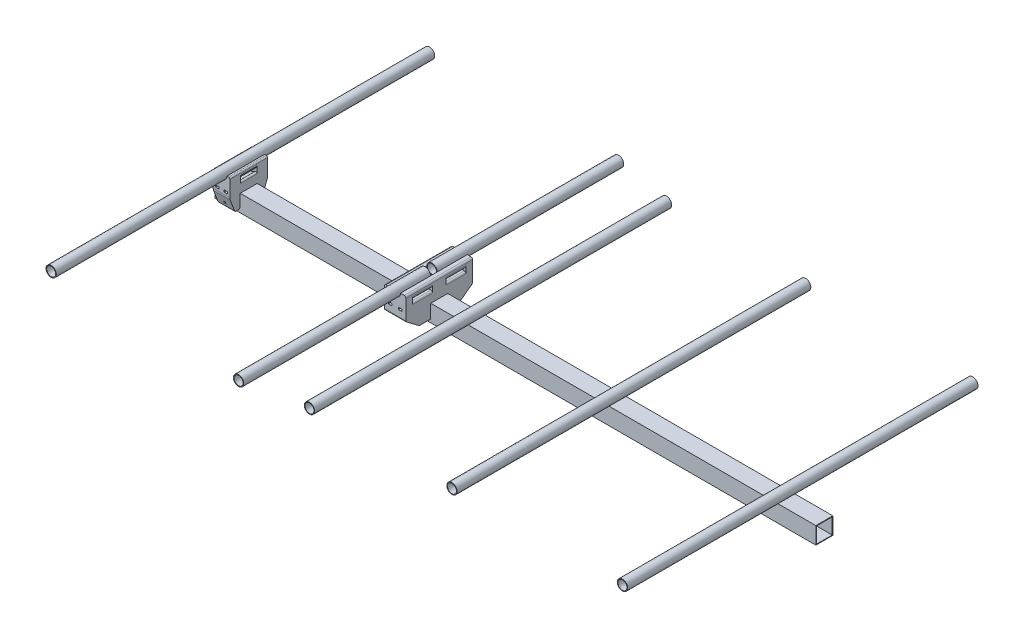
SolidWorks part; units mm, degrees
note: The reader was unsure of these and kept them because the rebuilt part matched: shared geometry of "Element Geometry<4>", "Element Geometry<5>", "Element Geometry<6>", "Element Geometry<7>".
other "Antenna Beam" parameters "D6"=81.8924, "D1"=79.9358, "D2"=111.825, "D3"=337.3911, "D4"=313.7423, "D5"=328.3888, "D7"=835, "D8"=23.25
ref_plane "Front Plane" through (0, 0, 0) normal (0, 0, 1) x (1, 0, 0)
ref_plane "Top Plane" through (0, 0, 0) normal (0, 1, 0) x (1, 0, 0)
ref_plane "Right Plane" through (0, 0, 0) normal (1, 0, 0) x (0, 0, -1)
sketch3d "3DSketch1"
  line L0 (-450, 0, 0) -> (450, 0, 0)
  point P4 (0, 0, 0)
  dimension "D1" = 900
other "Al tube square AL TUBE 1 SQR X 0.035 WALL(2)"
ref_plane "Plane2" through (-450, 0, 0) normal (1, 0, 0) x (0, 0, -1)
sketch "Sketch1" plane through (-450, 0, 0) normal (1, 0, 0) x (0, 0, -1)
  line L0 (-11.811, -11.811) -> (-11.811, 11.811)
  line L1 (11.811, 11.811) -> (-11.811, 11.811)
  line L2 (11.811, 11.811) -> (11.811, -11.811)
  line L3 (-11.811, -11.811) -> (11.811, -11.811)
  line L4 (-12.7, -12.7) -> (12.7, -12.7)
  line L5 (-12.7, -12.7) -> (-12.7, 12.7)
  line L6 (12.7, 12.7) -> (-12.7, 12.7)
  line L7 (12.7, 12.7) -> (12.7, -12.7)
  line L8 (0, -11.811) -> (0, -12.7) construction
  line L9 (0, -11.811) -> (0, 11.811) construction
  line L10 (0, 11.811) -> (0, 12.7) construction
  line L11 (12.7, 0) -> (11.811, 0) construction
  line L12 (11.811, 0) -> (-11.811, 0) construction
  line L13 (-11.811, 0) -> (-12.7, 0) construction
  point P14 (0, 0)
  point P17 (0, 0)
  dimension "Thickness" = 0.889
  dimension "V_leg" = 25.4
  dimension "H_leg" = 25.4
sketch "Element Geometry" plane through (0, 0, 0) normal (0, 0, 1) x (1, 0, 0)
  line L0 (-425, 113.5751) -> (-425, -79.8489) construction
  line L2 (-143, 160.4967) -> (-143, -91.5114) construction
  line L3 (-54, 179.3838) -> (-54, -96.4018) construction
  line L4 (157, 132.9645) -> (157, -180.7778) construction
  line L5 (-450, 12.7) -> (-450, -12.7) construction
  line L6 (410, 132.9645) -> (410, -195.4242) construction
  line L7 (-425, 40.45) -> (410, 40.45) construction
  line L11 (424.2916, 32.7) -> (387.9179, 32.7) construction
  line L12 (450, 12.7) -> (-450, 12.7) construction
  circle A0 centre (410, 40.45) radius 7.75
  circle A1 centre (157, 40.45) radius 7.75
  circle A2 centre (-425, 40.45) radius 7.75
  circle A3 centre (-143, 40.45) radius 7.75
  circle A4 centre (-54, 40.45) radius 7.75
  point P13 (157, 40.45)
  point P14 (-143, 40.45)
  point P18 (-54, 40.45)
  dimension "D2" = 282
  dimension "D3" = 371
  dimension "D4" = 582
extrude "Reflector Geometry" add sketch "Element Geometry" along normal mid plane 567 separate body contours A2
extrude "Director Geometry #1" add sketch "Element Geometry<4>" along normal mid plane 535 separate body contours A4
sketch "Element Geometry<4>" plane through (0, 0, 0) normal (0, 0, 1) x (1, 0, 0) same geometry as "Element Geometry"
extrude "Director Geometry #2" add sketch "Element Geometry<5>" along normal mid plane 530 separate body contours A1
sketch "Element Geometry<5>" plane through (0, 0, 0) normal (0, 0, 1) x (1, 0, 0) same geometry as "Element Geometry"
extrude "Director Geometry #3" add sketch "Element Geometry<6>" along normal mid plane 525 separate body contours A0
sketch "Element Geometry<6>" plane through (0, 0, 0) normal (0, 0, 1) x (1, 0, 0) same geometry as "Element Geometry"
extrude "Dipole-A" add sketch "Element Geometry<7>" along normal blind 279.7 from offset 5 separate body contours A3
sketch "Element Geometry<7>" plane through (0, 0, 0) normal (0, 0, 1) x (1, 0, 0) same geometry as "Element Geometry"
mirror "Dipole-B" about plane through (0, 0, 0) normal (0, 0, 1) of bodies 107
sketch "Sketch3" plane through (0, 0, 0) normal (0, 0, 1) x (1, 0, 0)
  line L0 (-433, 40.45) -> (-437.5, 40.45)
  line L1 (-437.5, 40.45) -> (-437.5, 12.7)
  line L2 (450, 12.7) -> (-450, 12.7) construction
  line L3 (-437.5, 12.7) -> (-412.5, 12.7)
  line L4 (-425, 12.7) -> (-425, 40.45) construction
  line L5 (-412.5, 40.45) -> (-412.5, 12.7)
  line L6 (-417, 40.45) -> (-412.5, 40.45)
  circle A0 centre (-425, 40.45) radius 7.75 construction
  circle A1 centre (-425, 40.45) radius 7.75 construction
  arc A2 (-433, 40.45) -> (-417, 40.45) centre (-425, 40.45) ccw
  arc A3 (-417, 40.45) -> (-433, 40.45) centre (-425, 40.45) ccw construction
  circle A4 centre (-425, 40.45) radius 8 construction
  dimension "D1" = 0.25
  dimension "D2" = 25
extrude "Element Base" add sketch "Sketch3" along normal offset from surface 0.5 and the other way offset from surface (13.2 mm away) 0.5 separate body up to face at (0, 0, 12.7) offset beyond the face yes other way up to face at (0, 0, -12.7)
sketch "Sketch4" plane through (0, 0, 13.2) normal (0, 0, 1) x (1, 0, 0)
  line L0 (-437.5, 12.7) -> (-437.5, -7.3)
  line L1 (-437.5, -7.3) -> (-412.5, -7.3)
  line L2 (-412.5, -7.3) -> (-412.5, 12.7)
  line L5 (-433, 40.45) -> (-437.5, 40.45)
  line L6 (-437.5, 40.45) -> (-437.5, 12.7)
  line L7 (-437.5, 12.7) -> (-412.5, 12.7)
  line L8 (-412.5, 12.7) -> (-412.5, 40.45)
  line L9 (-412.5, 40.45) -> (-417, 40.45)
  line L10 (-433, 40.45) -> (-437.5, 40.45)
  line L11 (-437.5, 40.45) -> (-437.5, 12.7)
  line L13 (-412.5, 12.7) -> (-412.5, 40.45)
  line L14 (-412.5, 40.45) -> (-417, 40.45)
  arc A1 (-433, 40.45) -> (-417, 40.45) centre (-425, 40.45) ccw
  arc A2 (-433, 40.45) -> (-417, 40.45) centre (-425, 40.45) ccw
  dimension "D2" = 20
  dimension "D1" = 0
extrude "Element Base Side" add sketch "Sketch4" along normal blind 15 from surface at 0 separate body starting at face at (-425, 29.8667, 13.2)
mirror "Mirror3" about plane through (0, 0, 0) normal (0, 0, 1) of bodies 110
combine bodies "Combine1" operation type add bodies to combine 111 109 110
ref_plane "Plane3" through (-425, 0, 0) normal (-1, 0, 0) x (0, 0, 1)
sketch "Sketch8" plane through (0, 0, 0) normal (0, 0, 1) x (1, 0, 0)
  line L0 (-437.5, 40.45) -> (-437.5, -7.3) construction
  line L1 (-412.5, -7.3) -> (-412.5, 40.45) construction
  line L2 (-412.5, 35.45) -> (-412.5, 29.7366)
  line L3 (-437.5, 35.45) -> (-437.5, 29.7366)
  arc A2 (-437.5, 35.45) -> (-412.5, 35.45) centre (-425, 40.45) ccw
  circle A3 centre (-425, 40.45) radius 7.75 construction
  circle A4 centre (-425, 40.45) radius 7.75 construction
  arc A5 (-437.5, 29.7366) -> (-412.5, 29.7366) centre (-425, 40.45) ccw
  arc A6 (-440.2854, 34.3358) -> (-437.5, 29.7366) centre (-425, 40.45) ccw construction
  arc A7 (-440.2854, 34.3358) -> (-409.7146, 34.3358) centre (-425, 40.45) ccw construction
  arc A8 (-412.5, 29.7366) -> (-409.7146, 34.3358) centre (-425, 40.45) ccw construction
  dimension "D1" = 5
  dimension "D2" = 3
extrude "Cut-Extrude3" cut sketch "Sketch8" along normal mid plane 25
sketch "Sketch9" plane through (0, 0, -28.2) normal (0, 0, -1) x (-1, 0, 0)
  line L0 (412.5, 12.7) -> (437.5, 12.7) construction
  line L1 (412.5, -7.3) -> (412.5, 40.45) construction
  line L2 (-450, 12.7) -> (450, 12.7) construction
  line L3 (437.5, 40.45) -> (437.5, -7.3) construction
  line L4 (425, 12.7) -> (425, -12.7) construction
  line L5 (-450, -12.7) -> (450, -12.7) construction
  circle A0 centre (425, 0) radius 1.5
  dimension "D1" = 3
extrude "Cut-Extrude4" cut sketch "Sketch9" against normal through all both and the other way through all
sketch "Sketch10" plane through (0, 0, 28.2) normal (0, 0, 1) x (1, 0, 0)
  line L0 (-425, 49.9101) -> (-425, -21.3409) construction
  line L1 (-437.5, 12.7) -> (-412.5, 12.7) construction
  line L2 (-437.5, 40.45) -> (-437.5, -7.3) construction
  line L3 (-412.5, -7.3) -> (-412.5, 40.45) construction
  line L4 (450, 12.7) -> (-450, 12.7) construction
  line L5 (-425, 32.45) -> (-437.5, 32.45) construction
  line L6 (-416.25, 20.7) -> (-416.25, 17.7)
  line L7 (-431.25, 12.7) -> (-431.25, 32.45) construction
  line L8 (-433.75, 20.7) -> (-428.75, 20.7)
  line L9 (-433.75, 20.7) -> (-433.75, 17.7)
  line L10 (-433.75, 17.7) -> (-428.75, 17.7)
  line L11 (-428.75, 20.7) -> (-428.75, 17.7)
  line L12 (-433.75, 20.7) -> (-428.75, 17.7) construction
  line L13 (-433.75, 17.7) -> (-428.75, 20.7) construction
  line L14 (-416.25, 17.7) -> (-421.25, 17.7)
  line L15 (-421.25, 20.7) -> (-421.25, 17.7)
  line L16 (-416.25, 20.7) -> (-421.25, 20.7)
  circle A2 centre (-425, 40.45) radius 7.75 construction
  circle A3 centre (-425, 40.45) radius 7.75 construction
  arc A4 (-433, 40.45) -> (-417, 40.45) centre (-425, 40.45) ccw construction
  point P19 (-431.25, 19.2)
  dimension "D1" = 3
  dimension "D2" = 5
  dimension "D3" = 5
extrude "Cut-Extrude5" cut sketch "Sketch10" against normal up to surface (56.4 mm away) from surface at 0 up to face at (-425, -1.5, -28.2) starting at face at (-425, 1.5, 28.2)
sketch "Sketch11" plane through (-437.5, 0, 0) normal (-1, 0, 0) x (0, 0, 1)
  line L0 (-20.7, -7.3) -> (-28.2, 12.7)
  line L1 (-28.2, -7.3) -> (-13.2, -7.3) construction
  line L2 (-28.2, 40.45) -> (-28.2, -7.3) construction
  line L3 (-28.2, 12.7) -> (-28.2, -7.3)
  line L4 (-28.2, -7.3) -> (-20.7, -7.3)
  line L5 (28.2, -7.3) -> (20.7, -7.3)
  line L6 (28.2, -7.3) -> (13.2, -7.3) construction
  line L7 (20.7, -7.3) -> (28.2, 12.7)
  line L8 (28.2, 40.45) -> (28.2, -7.3) construction
  line L9 (28.2, 12.7) -> (28.2, -7.3)
  dimension "D1" = 7.5
  dimension "D2" = 20
extrude "Cut-Extrude6" cut sketch "Sketch11" against normal up to surface (25 mm away) from surface at 0 up to face at (-412.5, 32.5933, 0) starting at face at (-437.5, 32.5933, 0)
fillet "Fillet3" radius 10 2 edges at (-425, 12.7, -28.2) (-425, 12.7, 28.2)
fillet "Fillet4" radius 2 4 edges at (-425, -7.3, -13.2) (-425, -7.3, 13.2) (-425, -7.3, 20.7) (-425, -7.3, -20.7)
fillet "Director Base" radius 2 4 edges at (-412.5, 40.45, 0) (-437.5, 40.45, 0) (-437.5, 29.7366, 0) (-412.5, 29.7366, 0)
sketch "Sketch12" plane through (0, 0, 0) normal (0, 0, 1) x (1, 0, 0)
  line L0 (-135, 40.45) -> (-127, 40.45)
  line L1 (-159, 40.45) -> (-159, 15.45)
  line L2 (-159, 15.45) -> (-127, 15.45)
  line L7 (-159, 40.45) -> (-151, 40.45)
  line L8 (-127, 40.45) -> (-127, 15.45)
  circle A0 centre (-143, 40.45) radius 8
  circle A1 centre (-143, 40.45) radius 7.75
  circle A2 centre (-143, 40.45) radius 7.75 construction
  dimension "D2" = 0.25
  dimension "D3" = 8
  dimension "D4" = 25
  dimension "D10" = 8
  dimension "D1" = 0
extrude "Boss-Extrude8" add sketch "Sketch12" along normal mid plane 100 separate body
sketch "Sketch16" plane through (0, 0, 0) normal (1, 0, 0) x (0, 0, -1)
  line L0 (13.2, 12.7) -> (-13.2, 12.7)
  line L1 (0, 0) -> (0, -50000) construction
  line L2 (12.7, 12.7) -> (-12.7, 12.7) construction
  line L3 (13.2, 12.7) -> (13.2, -7.7)
  line L4 (13.2, -7.7) -> (18.2, -7.7)
  line L5 (18.2, -7.7) -> (23.2, -2.7)
  line L6 (23.2, -2.7) -> (23.2, 15.45)
  line L7 (-50, 15.45) -> (50, 15.45) construction
  line L8 (-23.2, 15.45) -> (23.2, 15.45)
  line L9 (-23.2, -2.7) -> (-23.2, 15.45)
  line L10 (-18.2, -7.7) -> (-23.2, -2.7)
  line L11 (-13.2, -7.7) -> (-18.2, -7.7)
  line L12 (-13.2, 12.7) -> (-13.2, -7.7)
  line L13 (23.2, 15.45) -> (50, 15.45) construction
  line L14 (-50, 15.45) -> (-23.2, 15.45) construction
  point P7 (0, 12.7)
  dimension "D1" = 26.4
  dimension "D2" = 5
  dimension "D3" = 5
  dimension "D4" = 5
  dimension "D5" = 5
extrude "Boss-Extrude10" add sketch "Sketch16" against normal up to surface (32 mm away) from surface at -127 separate body up to face at (-159, 27.95, 0) starting at face at (-127, 27.95, 0)
combine bodies "Combine3" operation type add bodies to combine 120 127
sketch "Sketch17" plane through (-159, 0, 0) normal (-1, 0, 0) x (0, 0, 1)
  line L0 (-18.2, -7.7) -> (-50, -7.7)
  line L1 (-50, -7.7) -> (-50, 15.45)
  line L2 (-50, 15.45) -> (-23.2, 15.45)
  line L3 (-23.2, 15.45) -> (-23.2, -2.7)
  line L4 (-23.2, -2.7) -> (-18.2, -7.7)
  line L5 (0, 0) -> (0, -50000) construction
  line L6 (23.2, -2.7) -> (18.2, -7.7)
  line L7 (23.2, 15.45) -> (23.2, -2.7)
  line L8 (50, 15.45) -> (23.2, 15.45)
  line L9 (50, -7.7) -> (50, 15.45)
  line L10 (18.2, -7.7) -> (50, -7.7)
extrude "Boss-Extrude11" add sketch "Sketch17" against normal up to surface (32 mm away) from surface at 0 separate body up to face at (-127, 9.4214, 0) starting at face at (-159, 9.4214, 0)
combine bodies "Combine4" operation type add bodies to combine 130 128 129
sketch "Sketch18" plane through (-159, 0, 0) normal (-1, 0, 0) x (0, 0, 1)
  line L0 (-284.7, 32.7) -> (284.7, 32.7) construction
  line L1 (-50, 28.7) -> (50, 28.7) construction
  line L2 (-50, 40.45) -> (-50, -7.7) construction
  line L3 (50, -7.7) -> (50, 40.45) construction
  line L4 (0, 0) -> (0, -50000) construction
  line L5 (-40, 30.2) -> (-10, 30.2)
  line L6 (-40, 30.2) -> (-40, 27.2)
  line L7 (-40, 27.2) -> (-10, 27.2)
  line L8 (-10, 30.2) -> (-10, 27.2)
  line L9 (-40, 30.2) -> (-10, 27.2) construction
  line L10 (-40, 27.2) -> (-10, 30.2) construction
  line L11 (0, 0) -> (-50, 0) construction
  line L12 (-50, 0) -> (-25, 32.7) construction
  line L13 (-25, 32.7) -> (-25, 0) construction
  line L14 (40, 30.2) -> (40, 27.2)
  line L15 (40, 27.2) -> (10, 27.2)
  line L16 (10, 30.2) -> (10, 27.2)
  line L17 (40, 30.2) -> (10, 30.2)
  point P10 (-25, 28.7)
  dimension "D1" = 30
  dimension "D2" = 3
  dimension "D3" = 2.5
extrude "Cut-Extrude7" cut sketch "Sketch18" against normal up to next (32 mm away)
fillet "Fillet6" radius 5 4 edges at (-127, 30.2, -25) (-127, 30.2, 25) (-159, 30.2, 25) (-159, 30.2, -25)
fillet "Fillet7" radius 2.5 6 edges at (-159, 27.2, -25) (-159, 27.2, 25) (-159, 40.45, 0) (-127, 27.2, -25) (-127, 40.45, 0) (-127, 27.2, 25)
sketch "Sketch21" plane through (0, 0, 0) normal (0, 0, 1) x (1, 0, 0)
  line L0 (-433.75, 20.7) -> (-416.25, 17.7) construction
  line L1 (-416.25, 20.7) -> (-433.75, 17.7) construction
  line L2 (-425, 19.2) -> (0, 19.2) construction
  line L3 (0, 19.2) -> (0, 0) construction
  line L4 (-143, 40.45) -> (-143, -49959.55) construction
  line L5 (-133, 20.7) -> (-138, 17.7) construction
  line L6 (-153, 20.7) -> (-148, 20.7)
  line L7 (-153, 20.7) -> (-153, 17.7)
  line L8 (-153, 17.7) -> (-148, 17.7)
  line L9 (-148, 20.7) -> (-148, 17.7)
  line L10 (-153, 20.7) -> (-148, 17.7) construction
  line L11 (-153, 17.7) -> (-148, 20.7) construction
  line L12 (-133, 17.7) -> (-138, 20.7) construction
  line L13 (-133, 20.7) -> (-133, 17.7)
  line L14 (-133, 17.7) -> (-138, 17.7)
  line L15 (-138, 20.7) -> (-138, 17.7)
  line L16 (-133, 20.7) -> (-138, 20.7)
  circle A0 centre (-143, 40.45) radius 7.75 construction
  circle A1 centre (-143, 40.45) radius 7.75 construction
  point P8 (-425, 19.2)
  point P14 (-150.5, 19.2)
  point P27 (-135.5, 19.2)
  dimension "D1" = 15
  dimension "D2" = 3
  dimension "D3" = 5
extrude "Cut-Extrude8" cut sketch "Sketch21" against normal through all both and the other way through all
sketch "Sketch23" plane through (-159, 0, 0) normal (-1, 0, 0) x (0, 0, 1)
  line L0 (-50, 7.3) -> (-50, -7.7)
  line L1 (-50, 37.95) -> (-50, -7.7) construction
  line L2 (-50, -7.7) -> (-30, -7.7)
  line L3 (-50, -7.7) -> (-13.2, -7.7) construction
  line L4 (-30, -7.7) -> (-50, 7.3)
  line L5 (50, -7.7) -> (30, -7.7)
  line L8 (13.2, -7.7) -> (50, -7.7) construction
  line L9 (30, -7.7) -> (50, 7.3)
  line L10 (50, -7.7) -> (50, 37.95) construction
  line L11 (50, 7.3) -> (50, -7.7)
  dimension "D1" = 20
  dimension "D2" = 15
extrude "Cut-Extrude10" cut sketch "Sketch23" against normal up to next (32 mm away)
fillet "Dipole Base" radius 2.5 4 edges at (-143, -7.7, 30) (-143, 7.3, 50) (-143, -7.7, -30) (-143, 7.3, -50)
sketch "Sketch24" plane through (0, 0, 0) normal (0, 0, 1) x (1, 0, 0)
  circle A0 centre (410, 40.45) radius 7.75 construction
  circle A1 centre (-425, 40.45) radius 7.75
  circle A2 centre (-425, 40.45) radius 7.75 construction
  circle A3 centre (-54, 40.45) radius 7.75 construction
  circle A4 centre (157, 40.45) radius 7.75 construction
  circle A5 centre (-143, 40.45) radius 7.75 construction
  circle A6 centre (410, 40.45) radius 7.75 construction
  circle A7 centre (-54, 40.45) radius 7.75 construction
  circle A8 centre (157, 40.45) radius 7.75 construction
  circle A9 centre (-143, 40.45) radius 7.75 construction
  circle A10 centre (-425, 40.45) radius 6.75
  circle A11 centre (410, 40.45) radius 6.75
  circle A12 centre (-54, 40.45) radius 6.75
  circle A13 centre (157, 40.45) radius 6.75
  circle A14 centre (-143, 40.45) radius 6.75
  dimension "D1" = 0
  dimension "D2" = 1
extrude "Cut-Extrude11" cut sketch "Sketch24" against normal through all both and the other way through all
other "Save Bodies1"
equation "\"ReflectorLength\"= 567mm'Reflector Tube Length"
equation "\"DipolePosition\"= 282mm'Dipole Position"
equation "\"DiopleLeg\"= 279.7mm'Dipole Leg - lambda/4"
equation "\"DirectorPosition-1\"= 371mm'Director 1 - Position"
equation "\"DirectorLength-1\"= 535mm'Director 1 - Length"
equation "\"DirectorPosition-2\"= 582mm'Director 2 - Position"
equation "\"DirectorLength-2\"= 530mm'Director 2- Length"
equation "\"DirectorPosition-3\"= 835mm'Director 3 - Position"
equation "\"DirectorLength-3\"= 525mm'Directoe 3 - Length"
equation "\"D2@Element Geometry\" = \"DipolePosition\""
equation "\"D3@Element Geometry\" = \"DirectorPosition-1\""
equation "\"D4@Element Geometry\" = \"DirectorPosition-2\""
equation "\"D5@Element Geometry\" = \"DirectorPosition-3\""
equation "\"ReflectorOffset\"= 25mm'Reflector Offset from end of Beam"
equation "\"D1@Element Geometry\" = \"ReflectorOffset\""
equation "\"ElementHeight\"= 20mm'Element Height from Beam"
equation "\"ElementDiameter\"= 15.5mm'Copper Element Diameter"
equation "\"D6@Element Geometry\" = \"ElementDiameter\""
equation "\"D7@Element Geometry\"=\"ElementHeight\""
equation "\"D1@Reflector Geometry\" = \"ReflectorLength\""
equation "\"D1@Director Geometry #1\" = \"DirectorLength-1\""
equation "\"D1@Director Geometry #2\" = \"DirectorLength-2\""
equation "\"D1@Director Geometry #3\" = \"DirectorLength-3\""
equation "\"D1@Dipole-A\" = \"DiopleLeg\""
equation "\"Tolerance\"= 1mm'General Tolerance Variable"
equation "\"D1@Element Base\"=\"Tolerance\"/2"
equation "\"D2@Element Base\"=\"Tolerance\"/2"
